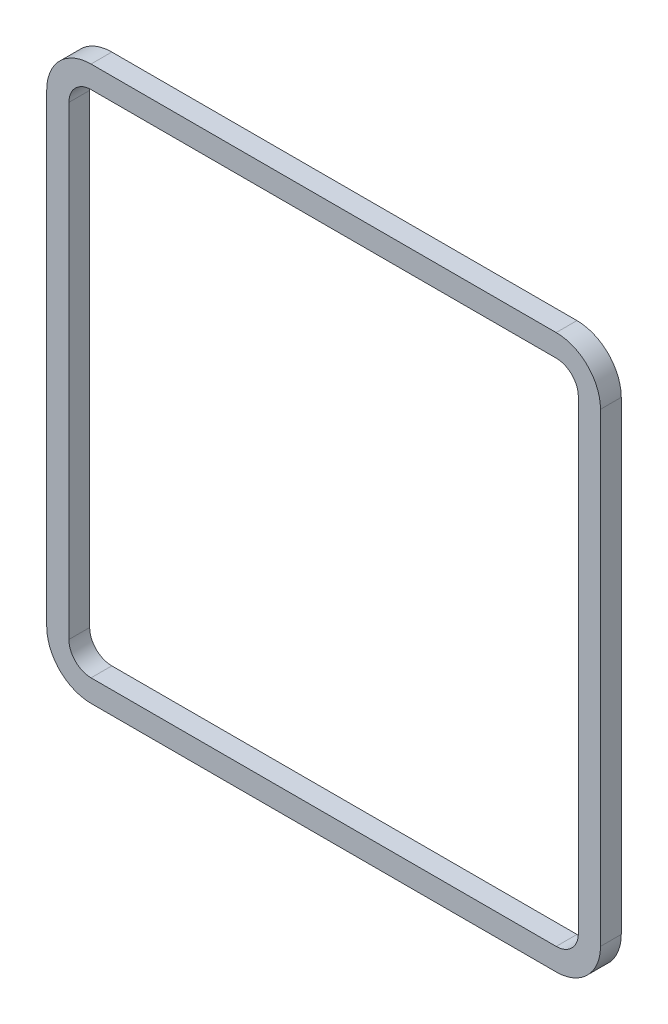
SolidWorks part; units mm, degrees
ref_plane "Front Plane" through (0, 0, 0) normal (0, 0, 1) x (1, 0, 0)
ref_plane "Top Plane" through (0, 0, 0) normal (0, 1, 0) x (1, 0, 0)
ref_plane "Right Plane" through (0, 0, 0) normal (1, 0, 0) x (0, 0, -1)
sketch "Sketch1" plane through (0, 0, 0) normal (0, 0, 1) x (1, 0, 0)
  line L0 (53.34, 58.42) -> (-53.34, 58.42)
  line L1 (53.34, 63.5) -> (-53.34, 63.5)
  line L2 (63.5, 53.34) -> (63.5, -53.34)
  line L3 (53.34, -63.5) -> (-53.34, -63.5)
  line L4 (-63.5, 53.34) -> (-63.5, -53.34)
  line L5 (63.5, 63.5) -> (-63.5, -63.5) construction
  line L6 (63.5, -63.5) -> (-63.5, 63.5) construction
  line L7 (-58.42, 53.34) -> (-58.42, -53.34)
  line L8 (53.34, -58.42) -> (-53.34, -58.42)
  line L9 (58.42, 53.34) -> (58.42, -53.34)
  arc A0 (63.5, 53.34) -> (53.34, 63.5) centre (53.34, 53.34) ccw
  arc A1 (53.34, -63.5) -> (63.5, -53.34) centre (53.34, -53.34) ccw
  arc A2 (-63.5, -53.34) -> (-53.34, -63.5) centre (-53.34, -53.34) ccw
  arc A3 (-53.34, 63.5) -> (-63.5, 53.34) centre (-53.34, 53.34) ccw
  arc A4 (-53.34, 58.42) -> (-58.42, 53.34) centre (-53.34, 53.34) ccw
  arc A5 (-58.42, -53.34) -> (-53.34, -58.42) centre (-53.34, -53.34) ccw
  arc A6 (53.34, -58.42) -> (58.42, -53.34) centre (53.34, -53.34) ccw
  arc A7 (58.42, 53.34) -> (53.34, 58.42) centre (53.34, 53.34) ccw
  point P0 (0, 0)
  dimension "D3" = 10.16
  dimension "D1" = 127
  dimension "D2" = 127
  dimension "D4" = 5.08
extrude "Boss-Extrude1" add sketch "Sketch1" along normal blind 4.7625
